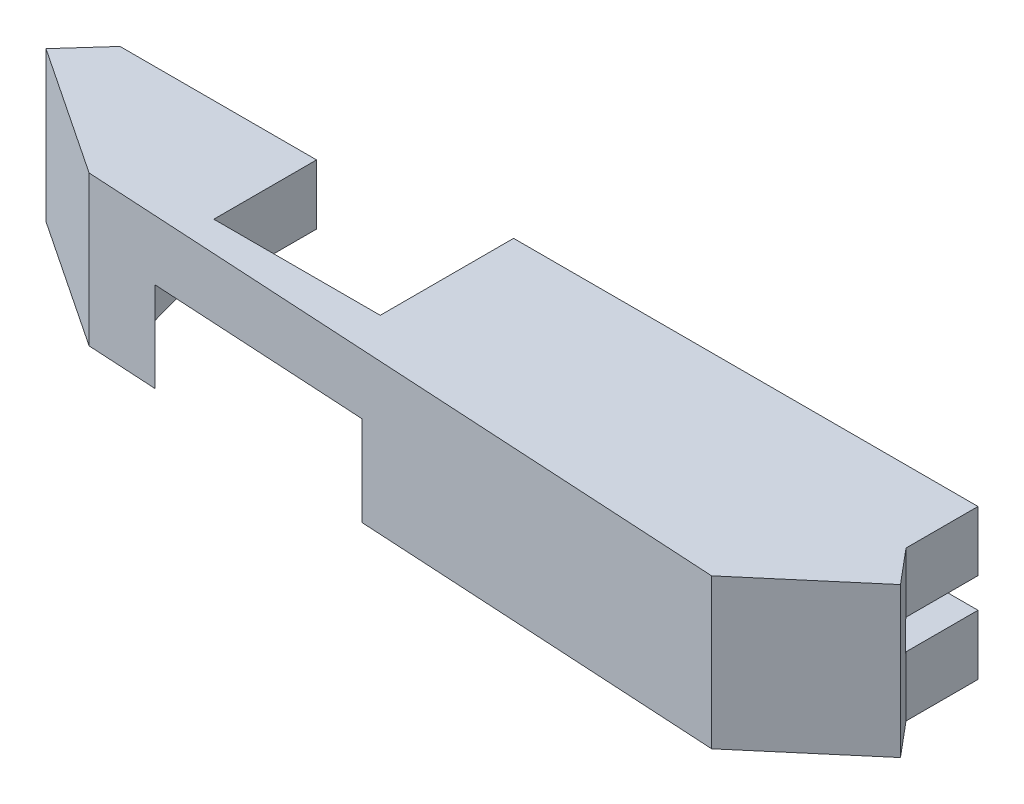
SolidWorks part; units mm, degrees
ref_plane "Front Plane" through (0, 0, 0) normal (0, 0, 1) x (1, 0, 0)
ref_plane "Top Plane" through (0, 0, 0) normal (0, 1, 0) x (1, 0, 0)
ref_plane "Right Plane" through (0, 0, 0) normal (1, 0, 0) x (0, 0, -1)
sketch "Sketch2" plane through (0, 0, 0) normal (0, 1, 0) x (1, 0, 0)
  line L0 (0, 0) -> (24.11, 0)
  line L1 (0, 0) -> (-7.6172, 6.8586)
  line L2 (24.11, 0) -> (34.41, 0)
  line L3 (29.26, 0) -> (29.26, 4.5)
  line L4 (29.26, 0) -> (29.26, 4.5)
  line L5 (29.26, 0) -> (29.26, -0.65)
  line L6 (34.41, 0) -> (42.73, 0)
  line L7 (42.73, 0) -> (47.61, 4.0948)
  line L8 (-7.6172, 6.8586) -> (5.5, 6.8586)
  line L9 (24.1512, 0) -> (16.61, 0)
  line L10 (16.61, 0) -> (16.61, 8.9)
  line L11 (16.61, 8.9) -> (47.61, 8.9)
  line L12 (47.61, 8.9) -> (47.61, 4.0948)
  line L13 (0, 0) -> (5.5, 0)
  line L14 (5.5, 0) -> (5.5, 6.8586)
  line L15 (0, 0) -> (-0.2007, -0.2229)
  line L16 (-7.6172, 6.8586) -> (-9.9592, 4.2576)
  line L17 (-9.9592, 4.2576) -> (-1.3383, -1.4863)
  line L18 (42.73, 0) -> (42.73, -0.3)
  line L19 (-1.3383, -1.4863) -> (42.73, -4)
  line L20 (47.61, 4.0948) -> (49.5384, 1.7967)
  line L21 (42.73, -4) -> (49.5384, 1.7967)
  line L22 (-7.6172, 6.8586) -> (-7.818, 6.6356)
  line L23 (-7.818, 6.6356) -> (-0.1152, -0.3)
  line L24 (0.2977, -0.6717) -> (0.2766, -0.6489)
  line L25 (29.26, 4.5) -> (29.26, 4.2)
  line L26 (42.73, 0) -> (42.73, -0.3)
  line L27 (42.73, -0.3) -> (-0.1152, -0.3)
  line L28 (-0.2701, -0.3) -> (-1.3383, -1.4863)
  line L29 (34.3688, -0.3) -> (34.1688, -0.3)
  line L30 (34.1688, -0.3) -> (34.1688, 0.6076)
  line L31 (24.1512, -0.3) -> (24.3512, -0.3)
  line L32 (24.3512, -0.3) -> (24.3512, 0.6076)
  line L33 (47.61, 4.0948) -> (47.8028, 3.865)
  line L34 (47.8028, 3.865) -> (42.8392, -0.3)
  line L35 (42.73, -0.3) -> (42.8392, -0.3)
  arc A0 (34.3688, 0) -> (24.1512, 0) centre (29.26, -0.65) ccw
  arc A1 (34.3688, -0.3) -> (24.1512, -0.3) centre (29.26, -0.95) ccw
  dimension "D1" = 24.11
  dimension "D2" = 10.25
  dimension "D3" = 138
  dimension "D4" = 10.3
  dimension "D5" = 4.5
  dimension "D6" = 0.65
  dimension "D7" = 8.32
  dimension "D8" = 140
  dimension "D9" = 7.5
  dimension "D10" = 8.9
  dimension "D11" = 31
  dimension "D12" = 5.5
  dimension "D13" = 90
  dimension "D14" = 2
  dimension "D15" = 90
  dimension "D16" = 3.5
  dimension "D17" = 4
  dimension "D18" = 3
  dimension "D19" = 90
  dimension "D20" = 0.3
  dimension "D21" = 0.3
  dimension "D22" = 0.2
  dimension "D23" = 0.2
  dimension "D24" = 0.3
extrude "Boss-Extrude2" add sketch "Sketch2" along normal blind 4 contours A0 L2 L6 L7 L12 L11 L10 L0 | L0 L14 L8 L1 | A1 L2 L0 L15 L23 L27 | A1 L2 A0 L4 | A1 L4 A0 L2 | L3 A1 L32 L2 | L30 A1 L3 L2 | L32 L27 L5 L2 | L27 L30 L2 L5 | L2 A1 L30 | L27 A1 L2 L30 | A1 L27 L18 L6 L2 | L35 L27 L23 L16 L17 L19 L21 L20 L34 | L32 A1 L2 | L2 A1 L27 L32 | L18 L35 L34 L20 L7 | L16 L23 L15 L1 region at (0.586, 0, -3.897) region at (-3.909, 0, -3.3178) region at (12.029, 0, 0.1501) region at (22.6521, 0, 0.6792) region at (31.9415, 0, -4.9712) region at (24.2617, 0, 0.1566) region at (25.901, 0, -3.1635) region at (26.8056, 0, 0.15) region at (24.2979, 0, -0.2106) region at (32.619, 0, -3.1635) region at (45.2248, 0, -1.8968) region at (31.7144, 0, 0.15) region at (27.1976, 0, -1.7623) region at (31.3224, 0, -1.7623) region at (38.5384, 0, 0.1499) region at (34.2583, 0, 0.1566) region at (34.2221, 0, -0.2106)
extrude "Boss-Extrude3" add sketch "Sketch2<9>" against normal blind 2 contours L35 L27 L23 L16 L17 L19 L21 L20 L34 | L3 A1 L32 L2 | L30 A1 L3 L2 | L27 L30 L2 L5 | L32 L27 L5 L2 region at (22.6521, 0, 0.6792) region at (26.8056, 0, 0.15) region at (31.7144, 0, 0.15) region at (27.1976, 0, -1.7623) region at (31.3224, 0, -1.7623)
sketch "Sketch2<9>" plane through (0, 0, 0) normal (0, 1, 0) x (1, 0, 0) same geometry as "Sketch2"
ref_plane "Plane2" through (0, -2, 0) normal (0, -1, 0) x (-1, 0, 0)
sketch "Sketch4" plane through (0, -2, 0) normal (0, -1, 0) x (-1, 0, 0)
  line L0 (0, 0) -> (0, 6.8586)
  line L2 (0, 6.8586) -> (7.6172, 6.8586)
  line L9 (-24.1512, 0) -> (-24.1512, 8.9)
  line L36 (-49.5384, 1.7967) -> (-48.2219, 0.6759)
  line L37 (-42.73, -4) -> (-49.5384, 1.7967) construction
  line L39 (-42.73, -0.3) -> (-42.8392, -0.3)
  line L40 (-47.8028, 3.865) -> (-42.8392, -0.3)
  line L41 (-47.61, 4.0948) -> (-47.8028, 3.865)
  line L43 (-24.1512, -0.3) -> (-24.3512, -0.3)
  line L44 (-34.1688, -0.3) -> (-34.1688, 0.6076)
  line L45 (-34.3688, -0.3) -> (-34.1688, -0.3)
  line L46 (0.2701, -0.3) -> (1.3383, -1.4863)
  line L47 (-42.73, -0.3) -> (0.1152, -0.3)
  line L48 (-42.73, 0) -> (-42.73, -0.3)
  line L49 (-29.26, 4.5) -> (-29.26, 4.2)
  line L50 (-0.2977, -0.6717) -> (-0.2766, -0.6489)
  line L51 (7.818, 6.6356) -> (0.1152, -0.3)
  line L52 (7.6172, 6.8586) -> (7.818, 6.6356)
  line L53 (-42.73, -4) -> (-49.5384, 1.7967)
  line L54 (-47.61, 4.0948) -> (-49.5384, 1.7967)
  line L55 (1.3383, -1.4863) -> (-42.73, -4)
  line L56 (-42.73, 0) -> (-42.73, -0.3)
  line L57 (9.9592, 4.2576) -> (1.3383, -1.4863)
  line L58 (7.6172, 6.8586) -> (9.9592, 4.2576)
  line L59 (0, 0) -> (0.2007, -0.2229)
  line L60 (-5.5, 0) -> (-5.5, 6.8586)
  line L61 (0, 0) -> (-5.5, 0)
  line L62 (-47.61, 8.9) -> (-47.61, 4.0948)
  line L63 (-16.61, 8.9) -> (-47.61, 8.9)
  line L64 (-16.61, 0) -> (-16.61, 8.9)
  line L65 (-24.1512, 0) -> (-16.61, 0)
  line L66 (7.6172, 6.8586) -> (-5.5, 6.8586)
  line L67 (-42.73, 0) -> (-47.61, 4.0948)
  line L68 (-34.41, 0) -> (-42.73, 0)
  line L69 (-29.26, 0) -> (-29.26, -0.65)
  line L70 (-29.26, 0) -> (-29.26, 4.5)
  line L71 (-29.26, 0) -> (-29.26, 4.5)
  line L72 (-24.11, 0) -> (-34.41, 0)
  line L73 (0, 0) -> (7.6172, 6.8586)
  line L74 (0, 0) -> (-24.11, 0)
  arc A2 (-34.3688, -0.3) -> (-24.1512, -0.3) centre (-29.26, -0.95) cw
  arc A3 (-34.3688, 0) -> (-24.1512, 0) centre (-29.26, -0.65) cw
extrude "Boss-Extrude4" add sketch "Sketch4" along normal blind 4 contours L0 L73 L2 | A3 L9 L63 L62 L67 L68 L72 | A2 L70 L72 | A2 L44 L72 L70 | A3 L72 A2 L49 | A3 L49 A2 L72 | A2 L72 L69 L47 L43 | L69 L72 L44 L47 | L58 L51 L47 L43 L45 L39 L40 L54 L36 L53 L55 L57 | L47 A2 L72 L68 L48 | L48 L67 L41 L40 L39 | A2 L72 L44 | A2 L45 L44 L72 | L72 A2 L47 L51 L59 L61 L74 L65 | L73 L59 L51 L52 region at (-3.909, -2, -3.3178) region at (12.029, -2, 0.1501) region at (-2.5391, -2, -4.5724) region at (22.6521, -2, 0.6792) region at (26.7166, -2, 0.1502) region at (25.9279, -2, -3.0657) region at (27.1884, -2, -1.7574) region at (36.6783, -2, -5.1847) region at (31.7144, -2, 0.15) region at (31.3224, -2, -1.7623) region at (32.3417, -2, -3.2609) region at (34.2583, -2, 0.1566) region at (34.2221, -2, -0.2106) region at (45.2248, -2, -1.8968) region at (38.5384, -2, 0.1499)
ref_plane "Plane3" through (0, -6, 0) normal (0, -1, 0) x (-1, 0, 0)
sketch "Sketch5" plane through (0, -6, 0) normal (0, -1, 0) x (-1, 0, 0)
  line L0 (0, 6.8586) -> (1.9043, 6.8586)
  line L3 (0, 0) -> (-0.6894, 0)
  line L4 (-0.6894, 0) -> (-0.6894, 6.8586)
  line L5 (7.6172, 6.8586) -> (-5.5, 6.8586) construction
  line L6 (-0.6894, 6.8586) -> (0, 6.8586)
  line L10 (-16.61, 8.9) -> (-47.61, 8.9) construction
  line L11 (-23.591, 8.9) -> (-23.591, 0)
  line L12 (0, 0) -> (-24.1512, 0) construction
  line L13 (-23.591, 0) -> (-24.1512, 0)
  line L14 (-24.1512, 0) -> (-25.659, 8.9)
  line L15 (-24.1512, 8.9) -> (-47.61, 8.9) construction
  line L16 (-25.659, 8.9) -> (-23.591, 8.9)
  line L17 (-23.591, 0) -> (-16.61, -3.2141)
  line L18 (-16.61, 0) -> (-5.5, 0)
  line L19 (-5.5, 0) -> (-11.055, 0)
  line L20 (-11.055, 0) -> (-11.055, -3.2141)
  line L21 (-16.61, 0) -> (-16.61, -3.2141)
  line L22 (-5.5, 0) -> (-5.5, -3.2141)
  line L23 (-5.5, -3.2141) -> (-0.6894, 0)
  line L24 (-16.61, -3.2141) -> (-5.5, -3.2141)
  line L25 (-23.591, 0) -> (-0.6894, 0)
  line L26 (-5.5, 0) -> (-0.6894, 0)
  line L27 (-0.9738, -1.6182) -> (-0.9735, -1.6182)
  line L28 (1.3383, -1.4863) -> (-42.73, -4) construction
  line L29 (0, 0) -> (1.9043, 6.8586)
extrude "Cut-Extrude1" cut sketch "Sketch5" against normal blind 6 contours L16 L14 L13 L11 | L25 L17 L21 | L21 L24 L20 L18 | L20 L24 L22 L18 | L25 L22 L23 | L3 L29 L0 L6 L4 region at (24.3201, -6, -5.301) region at (3.8965, -6, 1.0714) region at (-0.2234, -6, -4.0923) region at (8.2775, -6, 1.6071) region at (13.8325, -6, 1.6071) region at (18.937, -6, 1.0714)
